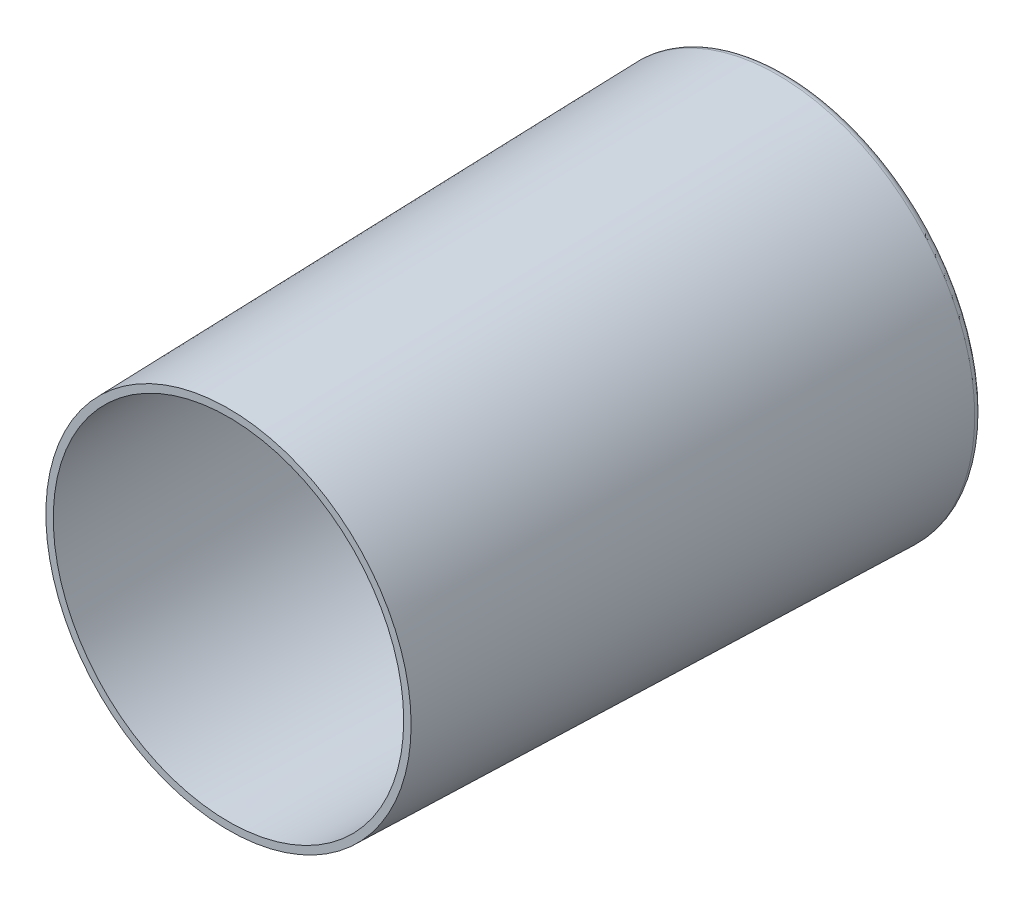
SolidWorks part; units mm, degrees
ref_plane "Front Plane" through (0, 0, 0) normal (0, 0, 1) x (1, 0, 0)
ref_plane "Top Plane" through (0, 0, 0) normal (0, 1, 0) x (1, 0, 0)
ref_plane "Right Plane" through (0, 0, 0) normal (1, 0, 0) x (0, 0, -1)
sketch "Sketch2" plane through (0, 0, 0) normal (0, 0, 1) x (1, 0, 0)
  line L0 (39.035, 38.989) -> (63.2672, 38.989) construction
  circle A3 centre (-10.948, 38.989) radius 49.983
  point P2 (39.035, 38.989)
  point P3 (0, 0)
  point P5 (0, 0)
extrude "Main part" add sketch "Sketch2" along normal blind 30 draft 1.5 and the other way blind 120 draft 1.5 contours A3
sketch "Sketch3" plane through (0, 0, 30) normal (0, 0, 1) x (1, 0, 0)
  circle A2 centre (-10.948, 38.989) radius 47.1974
  circle A3 centre (-10.948, 38.989) radius 47.1974
  dimension "D1" = 2
extrude "MainCut" cut sketch "Sketch3" against normal blind 150 draft 1.5 draft outward yes
fillet "Fillet1" radius 2 1 edges at (42.1773, 38.989, -120)
